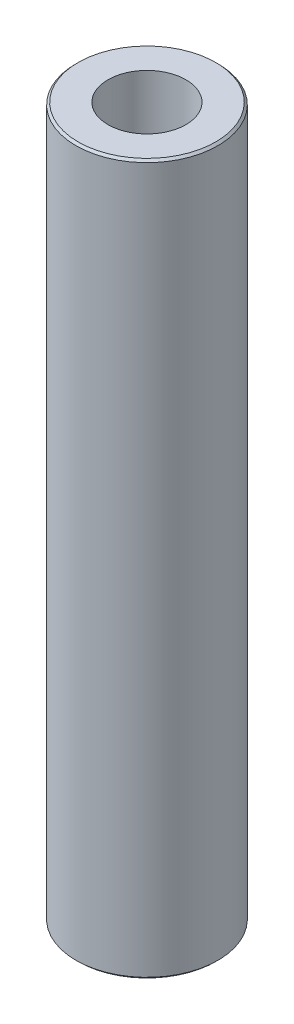
SolidWorks part; units mm, degrees
ref_plane "Front Plane" through (0, 0, 0) normal (0, 0, 1) x (1, 0, 0)
ref_plane "Top Plane" through (0, 0, 0) normal (0, 1, 0) x (1, 0, 0)
ref_plane "Right Plane" through (0, 0, 0) normal (1, 0, 0) x (0, 0, -1)
sketch "Sketch1" plane through (0, 0, 0) normal (0, 1, 0) x (1, 0, 0)
  circle A0 centre (0, 0) radius 60
  dimension "SHAFT_OD" = 120
extrude "Boss-Extrude1" add sketch "Sketch1" along normal blind 600
sketch "Sketch2" plane through (0, 0, 0) normal (0, 1, 0) x (1, 0, 0)
  circle A0 centre (0, 0) radius 32.9303
  dimension "BORE_D" = 65.8606
extrude "Cut-Extrude1" cut sketch "Sketch2" along normal through all
chamfer "Chamfer1" distance 1.8563 angle 44.56 2 edges at (0, 600, 60) (0, 0, 60) first distance on face at (0, 600, 60) first distance on face at (0, 0, 32.9303)
